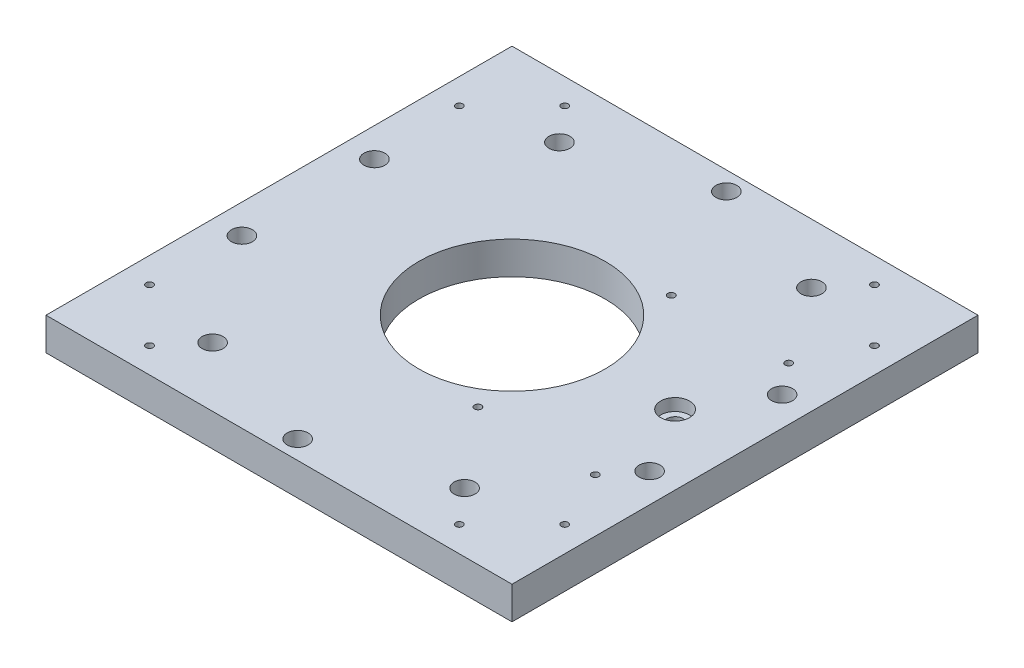
SolidWorks part; units mm, degrees
ref_plane "前视基准面" through (0, 0, 0) normal (0, 0, 1) x (1, 0, 0)
ref_plane "上视基准面" through (0, 0, 0) normal (0, 1, 0) x (1, 0, 0)
ref_plane "右视基准面" through (0, 0, 0) normal (1, 0, 0) x (0, 0, -1)
other "Configuration Table"
sketch "草图1" plane through (0, 0, 0) normal (0, 1, 0) x (1, 0, 0)
  line L1 (0, -50) -> (100, -50)
  line L2 (0, -50) -> (0, 50)
  line L3 (0, 50) -> (100, 50)
  line L4 (100, -50) -> (100, 50)
  circle A2 centre (85, 0) radius 1.75
  circle A4 centre (50, 0) radius 40
  circle A6 centre (85, 0) radius 3.1
  circle A7 centre (50, 0) radius 46
  circle A8 centre (50, 46) radius 2.25
  circle A9 centre (50, 46) radius 1.5
  circle A10 centre (50, 0) radius 50
  circle A11 centre (50, 0) radius 20
  point P0 (0, 0)
  point P15 (50, 50)
  point P20 (100, 0)
  dimension "D1" = 100
  dimension "D2" = 100
  dimension "D5" = 80
  dimension "D8" = 3.5
  dimension "D11" = 6.2
  dimension "D12" = 92
  dimension "D13" = 3
  dimension "D14" = 4.5
  dimension "D15" = 100
  dimension "D16" = 40
  dimension "D6" = 35
extrude "凸台-拉伸1" add sketch "草图1" along normal blind 7 contours L2 L3 L4 L1 | A2 | A11
extrude "切除-拉伸2" cut sketch "草图1<15>" against normal blind 2.6 from surface contours A6 starting at face at (85, 7, 1.75)
sketch "草图1<15>" plane through (0, 0, 0) normal (0, 1, 0) x (1, 0, 0) same geometry as "草图1"
extrude "切除-拉伸3" cut sketch "草图1<16>" along normal blind 2.6 contours A6
sketch "草图1<16>" plane through (0, 0, 0) normal (0, 1, 0) x (1, 0, 0) same geometry as "草图1"
extrude "切除-拉伸4" cut sketch "草图1<17>" along normal through all contours A9
sketch "草图1<17>" plane through (0, 0, 0) normal (0, 1, 0) x (1, 0, 0) same geometry as "草图1"
extrude "切除-拉伸5" cut sketch "草图1<18>" against normal offset from surface (5 mm away) 2 from surface contours A8 up to face at (50, 0, -44.5) starting at face at (50, 7, -44.5)
sketch "草图1<18>" plane through (0, 0, 0) normal (0, 1, 0) x (1, 0, 0) same geometry as "草图1"
pattern_circular "阵列(圆周)1" count 10 over 360 about axis through (50, 7, 0) along (0, -1, 0) of "切除-拉伸5", "切除-拉伸4"
sketch "草图2" plane through (0, 0, 0) normal (0, -1, 0) x (1, 0, 0)
  circle A0 centre (85, 9) radius 0.75
  circle A1 centre (85, -9) radius 0.75
  dimension "D1" = 1.5
extrude "切除-拉伸6" cut sketch "草图2" against normal blind 4 contours A0 | A1
sketch "草图3" plane through (0, 7, 0) normal (0, 1, 0) x (1, 0, 0)
  line L0 (0, 50) -> (100, -50)
  line L1 (0, -50) -> (100, 50)
  line L2 (16.766, 44.5477) -> (5.4523, 33.234)
  circle A0 centre (5.4523, 33.234) radius 0.75
  circle A1 centre (16.766, 44.5477) radius 0.75
  circle A2 centre (63.405, 20.7853) radius 0.75
  circle A3 centre (88.5848, 20.7853) radius 0.75
  circle A4 centre (63.405, -20.7147) radius 0.75
  circle A5 centre (88.5848, -20.7147) radius 0.75
  point P10 (11.1091, 38.8909)
  dimension "D3" = 1.5
  dimension "D4" = 1.5
  dimension "D1" = 8
  dimension "D2" = 55
extrude "切除-拉伸7" cut sketch "草图3" against normal through all contours A0 | A1
pattern_circular "阵列(圆周)2" count 4 over 360 about axis through (50, 7, 0) along (0, -1, 0) of "切除-拉伸7"
extrude "切除-拉伸8" cut sketch "草图3<3>" against normal through all contours A2 | A3 | A4 | A5
sketch "草图3<3>" plane through (0, 7, 0) normal (0, 1, 0) x (1, 0, 0) same geometry as "草图3"
